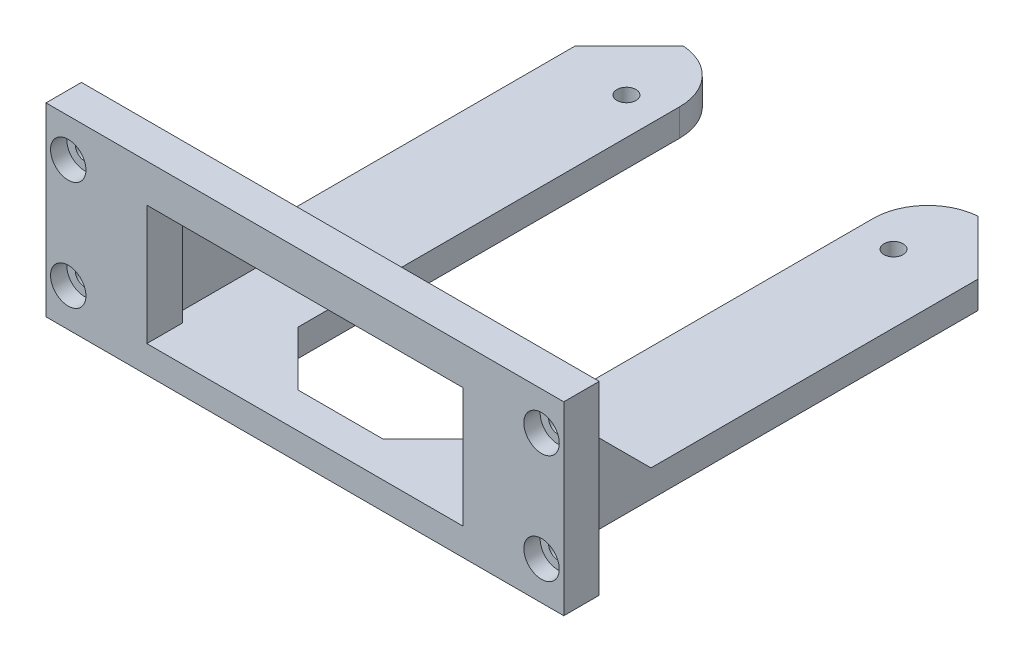
SolidWorks part; units mm, degrees
ref_plane "Front Plane" through (0, 0, 0) normal (0, 0, 1) x (1, 0, 0)
ref_plane "Top Plane" through (0, 0, 0) normal (0, 1, 0) x (1, 0, 0)
ref_plane "Right Plane" through (0, 0, 0) normal (1, 0, 0) x (0, 0, -1)
sketch "Sketch1" plane through (0, 0, 0) normal (0, 0, 1) x (1, 0, 0)
  line L1 (-47.5, 17) -> (47.5, 17)
  line L2 (-47.5, 17) -> (-47.5, -17)
  line L3 (-47.5, -17) -> (47.5, -17)
  line L4 (47.5, 17) -> (47.5, -17)
  line L5 (-47.5, 17) -> (47.5, -17) construction
  line L6 (-47.5, -17) -> (47.5, 17) construction
  point P0 (0, 0)
  dimension "D1" = 95
  dimension "D2" = 34
extrude "Boss-Extrude1" add sketch "Sketch1" along normal blind 6.5
sketch "Sketch2" plane through (0, 0, 0) normal (0, 0, -1) x (-1, 0, 0)
  line L0 (47.5, -17) -> (-47.5, -17) construction
  line L1 (-37, -17) -> (37, -17)
  line L2 (-37, -17) -> (-37, -12)
  line L3 (-37, -12) -> (37, -12)
  line L4 (37, -17) -> (37, -12)
  point P6 (0, -12)
  dimension "D1" = 74
  dimension "D2" = 5
extrude "Boss-Extrude2" add sketch "Sketch2" along normal blind 90
sketch "Sketch3" plane through (0, 0, 0) normal (0, 0, -1) x (-1, 0, 0)
  line L0 (37, -12) -> (-37, -12) construction
  line L1 (-29, -12) -> (29, -12)
  line L2 (-29, -12) -> (-29, 10)
  line L3 (-29, 10) -> (29, 10)
  line L4 (29, -12) -> (29, 10)
  point P6 (0, 10)
  dimension "D1" = 58
  dimension "D2" = 22
extrude "Cut-Extrude1" cut sketch "Sketch3" against normal blind 90
sketch "Sketch6" plane through (0, 0, 6.5) normal (0, 0, 1) x (1, 0, 0)
  point P0 (-43.42, 10)
  point P2 (-43.42, -10)
  point P4 (43.42, 10)
  point P6 (43.42, -10)
  dimension "D1" = 20
  dimension "D2" = 43.42
  dimension "D3" = 43.42
  dimension "D4" = 10
hole_wizard "CBORE for M3 SHCS1" positions "Sketch6" profile "Sketch5" counterbore size "M3" standard "ANSI Metric"
sketch "Sketch5" plane through (-43.42, 10, 6.5) normal (1, 0, 0) x (0, -1, 0)
  line L0 (0, 0) -> (0, 11.1215)
  line L1 (0, 11.1215) -> (1.7, 10.1)
  line L2 (1.7, 10.1) -> (1.7, 3)
  line L3 (1.7, 3) -> (3.25, 3)
  line L4 (3.25, 3) -> (3.25, 0)
  line L5 (3.25, 0) -> (0, 0)
  line L10 (0, 11.1215) -> (-1.7, 10.1) construction
  line L11 (0, -6.35) -> (0, 107.95) construction
  dimension "Hole Dia." = 3.4
  dimension "Hole Depth" = 10.1
  dimension "C'Bore Dia." = 6.5
  dimension "C'Bore Depth" = 3
  dimension "Drill Angle" = 118
sketch "Sketch7" plane through (0, 0, 0) normal (0, 0, -1) x (-1, 0, 0)
  line L0 (-29, 10) -> (-29, -12) construction
  line L9 (-37, -12) -> (-31, -12)
  line L10 (-37, -12) -> (-37, 8)
  line L11 (-37, 8) -> (-31, 8)
  line L12 (-31, -12) -> (-31, 8)
  line L13 (0, 18.7) -> (0, -18.7) construction
  line L14 (37, 8) -> (31, 8)
  line L15 (31, -12) -> (31, 8)
  line L16 (37, -12) -> (31, -12)
  line L17 (37, -12) -> (37, 8)
  dimension "D1" = 2
  dimension "D2" = 20
extrude "Boss-Extrude3" add sketch "Sketch7" along normal blind 20
chamfer "Chamfer1" distance 20 angle 45 2 edges at (34, 8, -20) (-34, 8, -20)
sketch "Sketch10" plane through (0, -12, 0) normal (0, 1, 0) x (1, 0, 0)
  line L0 (-29, -6.5) -> (29, -6.5) construction
  line L1 (0, -18.7) -> (0, 18.7) construction
  point P0 (-24.5, 77)
  point P2 (24.5, 77)
  point P4 (-24.5, 19)
  point P6 (24.5, 19)
  dimension "D1" = 58
  dimension "D2" = 49
  dimension "D3" = 25.5
  dimension "D4" = 24.5
hole_wizard "Ø1.0 (3.5) Diameter Hole1" positions "Sketch10" profile "Sketch11" hole size "Ø1.0" standard "ANSI Metric"
sketch "Sketch11" plane through (-24.5, -12, -77) normal (1, 0, 0) x (0, 0, 1)
  line L0 (0, 0) -> (0, 11.1515)
  line L1 (0, 11.1515) -> (1.75, 10.1)
  line L2 (1.75, 10.1) -> (1.75, 0)
  line L5 (1.75, 0) -> (0, 0)
  line L10 (0, 11.1515) -> (-1.75, 10.1) construction
  line L11 (0, -6.35) -> (0, 107.95) construction
  dimension "Hole Dia." = 3.5
  dimension "Hole Depth" = 10.1
  dimension "Drill Angle" = 118
sketch "Sketch12" plane through (0, -12, 0) normal (0, 1, 0) x (1, 0, 0)
  line L0 (-37, 90) -> (37, 90) construction
  line L1 (-17.75, 90) -> (17.75, 90)
  line L2 (-17.75, 90) -> (-17.75, 0)
  line L3 (-17.75, 0) -> (17.75, 0)
  line L4 (17.75, 90) -> (17.75, 0)
  line L5 (47.5, 0) -> (-47.5, 0) construction
  circle A1 centre (-24.5, 77) radius 1.75 construction
  circle A2 centre (24.5, 77) radius 1.75 construction
  dimension "D1" = 5
  dimension "D2" = 5
extrude "Cut-Extrude2" cut sketch "Sketch12" against normal blind 20
chamfer "Chamfer2" distance 10 angle 45 4 edges at (-17.75, -14.5, 0) (17.75, -14.5, 0) (37, -14.5, -90) (-37, -14.5, -90)
fillet "Fillet1" radius 10 2 edges at (-17.75, -14.5, -90) (17.75, -14.5, -90)
